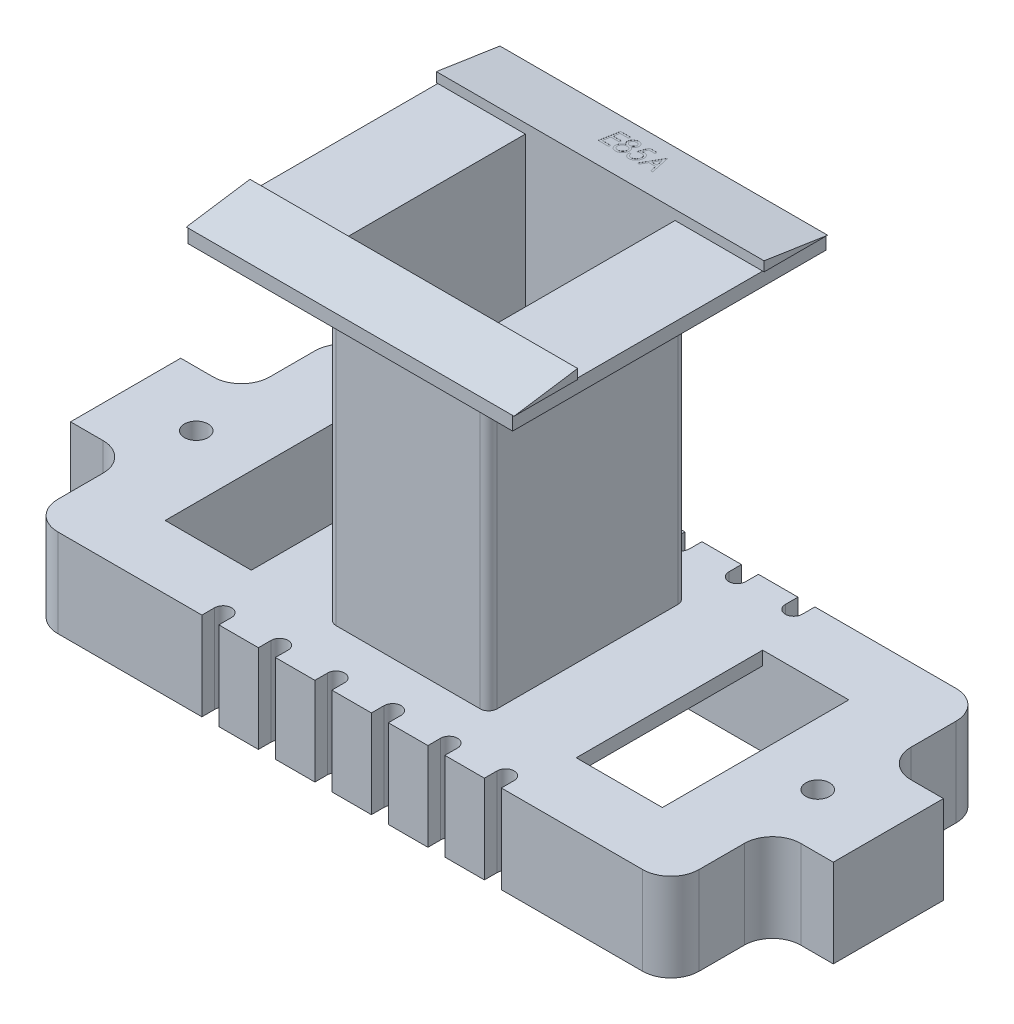
SolidWorks part; units mm, degrees
material "ABS"
ref_plane "Front Plane" through (0, 0, 0) normal (0, 0, 1) x (1, 0, 0)
ref_plane "Top Plane" through (0, 0, 0) normal (0, 1, 0) x (1, 0, 0)
ref_plane "Right Plane" through (0, 0, 0) normal (1, 0, 0) x (0, 0, -1)
sketch "Sketch2" plane through (0, 0, 0) normal (0, 1, 0) x (1, 0, 0)
  line L0 (14.25, -17.5) -> (14.25, 17.5)
  line L5 (13.25, -16.5) -> (-13.25, -16.5)
  line L6 (13.25, -16.5) -> (13.25, 16.5)
  line L11 (13.25, 16.5) -> (-13.25, 16.5)
  line L12 (-13.25, -16.5) -> (-13.25, 16.5)
  line L13 (13.25, -16.5) -> (-13.25, 16.5) construction
  line L14 (13.25, 16.5) -> (-13.25, -16.5) construction
  line L15 (14.25, 17.5) -> (-14.25, 17.5)
  line L16 (-14.25, -17.5) -> (-14.25, 17.5)
  line L17 (14.25, -17.5) -> (-14.25, -17.5)
  point P0 (0, 0)
  point P1 (0, 0)
  point P5 (0, 0)
  dimension "D1" = 33
  dimension "D2" = 26.5
  dimension "D3" = 1
extrude "Boss-Extrude1" add sketch "Sketch2" along normal mid plane 55.7
sketch "Sketch4" plane through (0, 27.85, 0) normal (0, 1, 0) x (1, 0, 0)
  line L1 (-28.75, -27.75) -> (28.75, -27.75)
  line L2 (-28.75, -27.75) -> (-28.75, 27.75)
  line L3 (-28.75, 27.75) -> (28.75, 27.75)
  line L4 (28.75, -27.75) -> (28.75, 27.75)
  line L5 (-28.75, -27.75) -> (28.75, 27.75) construction
  line L6 (-28.75, 27.75) -> (28.75, -27.75) construction
  line L14 (13.25, -16.5) -> (13.25, 16.5) construction
  line L15 (-13.25, -16.5) -> (13.25, -16.5) construction
  line L16 (-13.25, 16.5) -> (-13.25, -16.5) construction
  line L17 (13.25, 16.5) -> (-13.25, 16.5) construction
  line L18 (13.25, -16.5) -> (13.25, 16.5)
  line L19 (-13.25, -16.5) -> (13.25, -16.5)
  line L20 (-13.25, 16.5) -> (-13.25, -16.5)
  line L21 (13.25, 16.5) -> (-13.25, 16.5)
  point P0 (0, 0)
  dimension "D1" = 57.5
  dimension "D2" = 55.5
extrude "Boss-Extrude2" add sketch "Sketch4" along normal blind 2.4
mirror "Mirror1" about plane through (0, 0, 0) normal (0, 1, 0) of "Boss-Extrude2"
fillet "Fillet1" radius 1.5 4 edges at (-14.25, 0, 17.5) (-14.25, 0, -17.5) (14.25, 0, -17.5) (14.25, 0, 17.5)
sketch "Sketch5" plane through (0, 0, 0) normal (1, 0, 0) x (0, 0, -1)
  line L0 (-27.75, 30.25) -> (-16.5, 31.95)
  line L1 (-16.5, 31.95) -> (-16.5, 30.25)
  line L2 (-27.75, 30.25) -> (27.75, 30.25) construction
  line L4 (-16.5, 30.25) -> (-27.75, 30.25)
  line L5 (0, 0) -> (0, 38.1311) construction
  line L7 (27.75, 30.25) -> (16.5, 31.95)
  line L8 (16.5, 30.25) -> (27.75, 30.25)
  line L10 (-16.5, 30.25) -> (-16.5, -30.25) construction
  line L11 (16.5, 31.95) -> (16.5, 30.25)
  dimension "D1" = 1.7
extrude "Boss-Extrude3" add sketch "Sketch5" along normal mid plane 58
sketch "Sketch9" plane through (0, 33.6744, -5.0886) normal (0, 0.9888, -0.1494) x (1, 0, 0)
  line L0 (-29, 16.041) -> (29, 16.041) construction
  line L3 (29, 22.9187) -> (29, 11.541) construction
  line L4 (29, 11.541) -> (-29, 11.541) construction
  line L5 (-29, 22.9187) -> (-29, 11.541) construction
  text T0 "E85A" font "Century Gothic" height 4
  dimension "D1" = 4.5
extrude "Cut-Extrude2" cut sketch "Sketch9" against normal blind 0.01
sketch "Sketch8" plane through (0, -30.25, 0) normal (0, -1, 0) x (1, 0, 0)
  line L1 (-28.75, -27.75) -> (28.75, -27.75)
  line L2 (28.75, -27.75) -> (28.75, -16.5)
  line L37 (28.75, -16.5) -> (-28.75, -16.5)
  line L42 (-28.75, -16.5) -> (-28.75, -27.75)
  line L58 (0, 0) -> (37.0568, 0) construction
  line L79 (-28.75, 16.5) -> (-28.75, 27.75)
  line L82 (28.75, 16.5) -> (-28.75, 16.5)
  line L83 (28.75, 27.75) -> (28.75, 16.5)
  line L84 (-28.75, 27.75) -> (28.75, 27.75)
extrude "Boss-Extrude4" add sketch "Sketch8" along normal blind 13.2
sketch "Sketch11" plane through (0, -43.45, 0) normal (0, -1, 0) x (1, 0, 0)
  line L0 (0, 8.5975) -> (0, -6.374) construction
  line L3 (0, 0) -> (9.2559, 0) construction
  line L4 (28.75, 16.5) -> (44, 16.5)
  line L5 (28.75, -16.5) -> (44, -16.5)
  line L6 (44, 16.5) -> (44, -16.5)
  line L7 (28.75, 27.75) -> (28.75, 16.5)
  line L8 (13.25, 16.5) -> (28.75, 16.5) construction
  line L11 (28.75, -27.75) -> (28.75, -16.5)
  line L21 (28.75, 27.75) -> (51.75, 27.75)
  line L22 (56.75, 22.75) -> (56.75, 14.75)
  line L23 (61.75, 9.75) -> (67.5, 9.75)
  line L24 (67.5, -9.75) -> (67.5, 9.75)
  line L25 (61.75, -9.75) -> (67.5, -9.75)
  line L26 (56.75, -22.75) -> (56.75, -14.75)
  line L27 (28.75, -27.75) -> (51.75, -27.75)
  line L30 (-28.75, -27.75) -> (-51.75, -27.75)
  line L31 (-56.75, -22.75) -> (-56.75, -14.75)
  line L32 (-61.75, -9.75) -> (-67.5, -9.75)
  line L33 (-67.5, -9.75) -> (-67.5, 9.75)
  line L34 (-61.75, 9.75) -> (-67.5, 9.75)
  line L35 (-56.75, 22.75) -> (-56.75, 14.75)
  line L36 (-28.75, 27.75) -> (-51.75, 27.75)
  line L37 (-28.75, -27.75) -> (-28.75, -16.5)
  line L40 (-28.75, 27.75) -> (-28.75, 16.5)
  line L41 (-44, 16.5) -> (-44, -16.5)
  line L42 (-28.75, -16.5) -> (-44, -16.5)
  line L43 (-28.75, 16.5) -> (-44, 16.5)
  circle A3 centre (55, 0) radius 2.1
  arc A8 (51.75, -27.75) -> (56.75, -22.75) centre (51.75, -22.75) ccw
  arc A9 (56.75, -14.75) -> (61.75, -9.75) centre (61.75, -14.75) cw
  arc A10 (56.75, 22.75) -> (51.75, 27.75) centre (51.75, 22.75) ccw
  arc A11 (56.75, 14.75) -> (61.75, 9.75) centre (61.75, 14.75) ccw
  arc A14 (-56.75, 14.75) -> (-61.75, 9.75) centre (-61.75, 14.75) cw
  arc A15 (-56.75, 22.75) -> (-51.75, 27.75) centre (-51.75, 22.75) cw
  arc A16 (-56.75, -14.75) -> (-61.75, -9.75) centre (-61.75, -14.75) ccw
  arc A17 (-51.75, -27.75) -> (-56.75, -22.75) centre (-51.75, -22.75) cw
  circle A18 centre (-55, 0) radius 2.1
  point P48 (67.5, 0)
  point P52 (56.75, -27.75)
  point P55 (56.75, -9.75)
  point P58 (56.75, 27.75)
  point P61 (56.75, 9.75)
  point P76 (-56.75, 9.75)
  point P77 (-56.75, 27.75)
  point P78 (-56.75, -9.75)
  point P79 (-56.75, -27.75)
  point P80 (-67.5, 0)
  dimension "D1" = 55
  dimension "D3" = 4.2
  dimension "D7" = 28
  dimension "D9" = 5
  dimension "D2" = 23.5
  dimension "D4" = 44
  dimension "D8" = 18
extrude "Boss-Extrude5" add sketch "Sketch11" against normal up to surface (15.6 mm away) up to face at (0, -27.85, 0)
sketch "Sketch7" plane through (0, -30.25, 0) normal (0, -1, 0) x (1, 0, 0)
  line L0 (0, 0) -> (0, 58.3367) construction
  line L2 (-28.75, -16.5) -> (-28.75, 16.5) construction
  line L7 (0, 0) -> (-44.9899, 0) construction
  line L23 (-29, 28) -> (29, 28) construction
  line L24 (-26.25, 25.5) -> (-26.25, 28)
  line L25 (-26.25, -25.5) -> (-26.25, -28)
  line L26 (-26.25, 28) -> (-23.25, 28)
  line L27 (-26.25, -28) -> (-23.25, -28)
  line L28 (-23.25, 28) -> (-23.25, 25.5)
  line L29 (-23.25, -28) -> (-23.25, -25.5)
  line L31 (-16.25, 25.5) -> (-16.25, 28)
  line L32 (-16.25, 28) -> (-13.25, 28)
  line L33 (-13.25, 28) -> (-13.25, 25.5)
  line L34 (-6.25, 25.5) -> (-6.25, 28)
  line L35 (-6.25, 28) -> (-3.25, 28)
  line L36 (-3.25, 28) -> (-3.25, 25.5)
  line L37 (3.75, 25.5) -> (3.75, 28)
  line L38 (3.75, 28) -> (6.75, 28)
  line L39 (6.75, 28) -> (6.75, 25.5)
  line L40 (13.75, 25.5) -> (13.75, 28)
  line L41 (13.75, 28) -> (16.75, 28)
  line L42 (16.75, 28) -> (16.75, 25.5)
  line L43 (23.75, 25.5) -> (23.75, 28)
  line L44 (23.75, 28) -> (26.75, 28)
  line L45 (26.75, 28) -> (26.75, 25.5)
  line L46 (-16.25, -25.5) -> (-16.25, -28)
  line L47 (-13.25, -28) -> (-13.25, -25.5)
  line L48 (-16.25, -28) -> (-13.25, -28)
  line L49 (-6.25, -25.5) -> (-6.25, -28)
  line L50 (-3.25, -28) -> (-3.25, -25.5)
  line L51 (-6.25, -28) -> (-3.25, -28)
  line L52 (3.75, -25.5) -> (3.75, -28)
  line L53 (6.75, -28) -> (6.75, -25.5)
  line L54 (3.75, -28) -> (6.75, -28)
  line L55 (13.75, -25.5) -> (13.75, -28)
  line L56 (16.75, -28) -> (16.75, -25.5)
  line L57 (13.75, -28) -> (16.75, -28)
  line L58 (23.75, -25.5) -> (23.75, -28)
  line L59 (26.75, -28) -> (26.75, -25.5)
  line L60 (23.75, -28) -> (26.75, -28)
  arc A0 (-26.25, 25.5) -> (-23.25, 25.5) centre (-24.75, 25.5) ccw
  arc A1 (-16.25, 25.5) -> (-13.25, 25.5) centre (-14.75, 25.5) ccw
  arc A2 (-6.25, 25.5) -> (-3.25, 25.5) centre (-4.75, 25.5) ccw
  arc A3 (3.75, 25.5) -> (6.75, 25.5) centre (5.25, 25.5) ccw
  arc A4 (13.75, 25.5) -> (16.75, 25.5) centre (15.25, 25.5) ccw
  arc A5 (23.75, 25.5) -> (26.75, 25.5) centre (25.25, 25.5) ccw
  arc A6 (23.75, -25.5) -> (26.75, -25.5) centre (25.25, -25.5) cw
  arc A7 (13.75, -25.5) -> (16.75, -25.5) centre (15.25, -25.5) cw
  arc A8 (3.75, -25.5) -> (6.75, -25.5) centre (5.25, -25.5) cw
  arc A9 (-6.25, -25.5) -> (-3.25, -25.5) centre (-4.75, -25.5) cw
  arc A10 (-16.25, -25.5) -> (-13.25, -25.5) centre (-14.75, -25.5) cw
  arc A11 (-26.25, -25.5) -> (-23.25, -25.5) centre (-24.75, -25.5) cw
  arc A12 (-23.25, 25.5) -> (-26.25, 25.5) centre (-24.75, 25.5) ccw construction
  arc A13 (-13.25, 25.5) -> (-16.25, 25.5) centre (-14.75, 25.5) ccw construction
  arc A14 (-3.25, 25.5) -> (-6.25, 25.5) centre (-4.75, 25.5) ccw construction
  arc A15 (6.75, 25.5) -> (3.75, 25.5) centre (5.25, 25.5) ccw construction
  arc A16 (16.75, 25.5) -> (13.75, 25.5) centre (15.25, 25.5) ccw construction
  arc A17 (26.75, 25.5) -> (23.75, 25.5) centre (25.25, 25.5) ccw construction
  arc A18 (-23.25, -25.5) -> (-26.25, -25.5) centre (-24.75, -25.5) cw construction
  arc A19 (-13.25, -25.5) -> (-16.25, -25.5) centre (-14.75, -25.5) cw construction
  arc A20 (-3.25, -25.5) -> (-6.25, -25.5) centre (-4.75, -25.5) cw construction
  arc A21 (6.75, -25.5) -> (3.75, -25.5) centre (5.25, -25.5) cw construction
  arc A22 (16.75, -25.5) -> (13.75, -25.5) centre (15.25, -25.5) cw construction
  arc A23 (26.75, -25.5) -> (23.75, -25.5) centre (25.25, -25.5) cw construction
  dimension "D1" = 3
  dimension "D6" = 6
  dimension "D2" = 4
  dimension "D3" = 2.5
  dimension "D4" = 6
  dimension "D5" = 2.5
  dimension "D7" = 6
extrude "Cut-Extrude1" cut sketch "Sketch7" against normal mid plane 33
